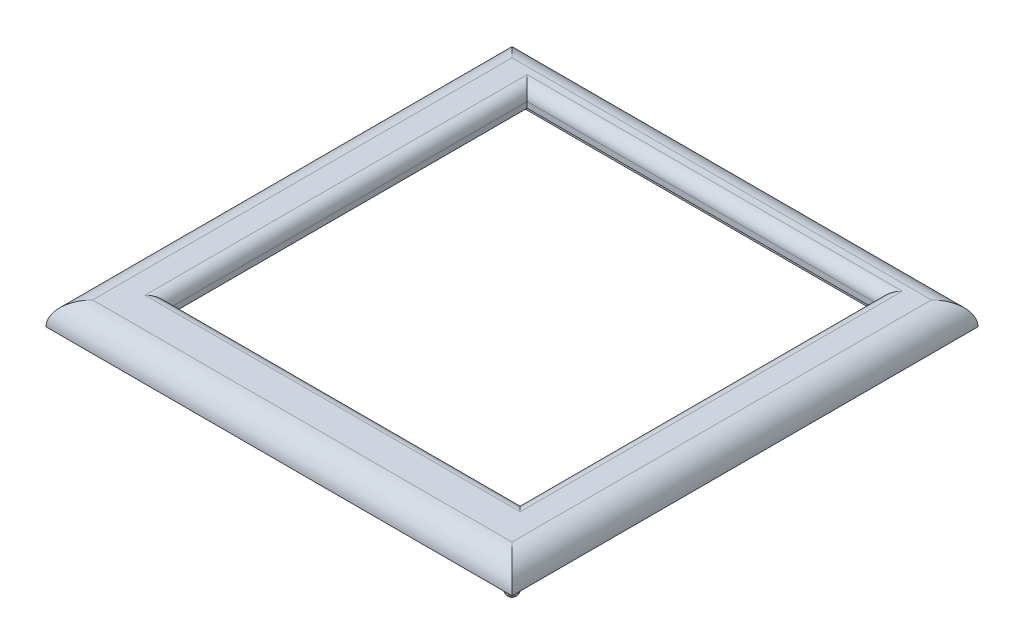
SolidWorks part; units mm, degrees
ref_plane "前视基准面" through (0, 0, 0) normal (0, 0, 1) x (1, 0, 0)
ref_plane "上视基准面" through (0, 0, 0) normal (0, 1, 0) x (1, 0, 0)
ref_plane "右视基准面" through (0, 0, 0) normal (1, 0, 0) x (0, 0, -1)
sketch "草图1" plane through (0, 0, 0) normal (0, 1, 0) x (1, 0, 0)
  line L1 (-20, -20) -> (20, -20)
  line L2 (-20, -20) -> (-20, 20)
  line L3 (-20, 20) -> (20, 20)
  line L4 (20, -20) -> (20, 20)
  line L5 (-20, -20) -> (20, 20) construction
  line L6 (-20, 20) -> (20, -20) construction
  line L7 (-15.1, 16.4) -> (15.1, 16.4)
  line L8 (-15.1, 16.4) -> (-15.1, -14.4)
  line L9 (-15.1, -14.4) -> (15.1, -14.4)
  line L10 (15.1, 16.4) -> (15.1, -14.4)
  line L11 (-15.1, 16.4) -> (15.1, -14.4) construction
  line L12 (-15.1, -14.4) -> (15.1, 16.4) construction
  point P0 (0, 0)
  point P6 (0, 1)
  dimension "D1" = 40
  dimension "D2" = 40
  dimension "D3" = 1
  dimension "D4" = 30.2
  dimension "D5" = 30.8
extrude "凸台-拉伸1" add sketch "草图1" along normal blind 2
sketch "草图2" plane through (0, 0, 0) normal (0, -1, 0) x (1, 0, 0)
  line L1 (15.8, 16.75) -> (-15.8, 16.75)
  line L2 (15.8, 16.75) -> (15.8, -16.75)
  line L3 (15.8, -16.75) -> (-15.8, -16.75)
  line L4 (-15.8, 16.75) -> (-15.8, -16.75)
  line L5 (15.8, 16.75) -> (-15.8, -16.75) construction
  line L6 (15.8, -16.75) -> (-15.8, 16.75) construction
  point P0 (0, 0)
  dimension "D1" = 31.6
  dimension "D2" = 33.5
extrude "切除-拉伸1" cut sketch "草图2" against normal blind 0.5
sketch "草图3" plane through (0, 0.5, 0) normal (0, -1, 0) x (1, 0, 0)
  line L0 (0, 14.4) -> (0, 16.75) construction
  line L1 (-15.1, 14.4) -> (15.1, 14.4) construction
  line L2 (15.8, 16.75) -> (-15.8, 16.75) construction
  line L4 (8, 14.4) -> (-8, 14.4)
  line L5 (8, 14.4) -> (8, 15.6)
  line L6 (8, 15.6) -> (-8, 15.6)
  line L7 (-8, 14.4) -> (-8, 15.6)
  line L8 (8, 14.4) -> (-8, 15.6) construction
  line L9 (8, 15.6) -> (-8, 14.4) construction
  point P6 (0, 15)
  dimension "D1" = 16
  dimension "D2" = 1.2
  dimension "D3" = 0
extrude "切除-拉伸2" cut sketch "草图3" against normal blind 0.5
fillet "圆角1" radius 1 4 edges at (15.1, 2, -1) (0, 2, 14.4) (0, 2, -16.4) (-15.1, 2, -1)
fillet "圆角2" radius 2 4 edges at (0, 2, -20) (20, 2, 0) (0, 2, 20) (-20, 2, 0)
sketch "草图4" plane through (0, 0, 0) normal (0, -1, 0) x (1, 0, 0)
  line L0 (20, -20) -> (-20, -20) construction
  line L1 (-20, -20) -> (-20, 20) construction
  line L2 (-20, 20) -> (20, 20) construction
  line L4 (20, 20) -> (20, -20) construction
  circle A0 centre (-19, -19) radius 0.5
  circle A1 centre (19, 19) radius 0.5
  dimension "D1" = 1
  dimension "D5" = 1
  dimension "D2" = 1
  dimension "D3" = 1
  dimension "D4" = 1
extrude "凸台-拉伸2" add sketch "草图4" along normal blind 1
fillet "圆角4" radius 0.5 1 edges at (19, -1, 18.5)
sketch "草图5" plane through (0, 0, 0) normal (0, -1, 0) x (1, 0, 0)
  line L0 (20, -20) -> (-20, -20) construction
  line L1 (20, 20) -> (20, -20) construction
  line L2 (-20, -20) -> (-20, 20) construction
  line L3 (-20, 20) -> (20, 20) construction
  circle A0 centre (19, -19) radius 0.5
  circle A1 centre (-19, 19) radius 0.5
  dimension "D3" = 1
  dimension "D6" = 1
  dimension "D1" = 1
  dimension "D2" = 1
  dimension "D4" = 1
  dimension "D5" = 1
extrude "切除-拉伸3" cut sketch "草图5" against normal blind 1
fillet "圆角5" radius 0.5 2 edges at (19, 1, -19.5) (-19, 1, 18.5)
fillet "圆角6" radius 0.5 1 edges at (-19, -1, -19.5)
